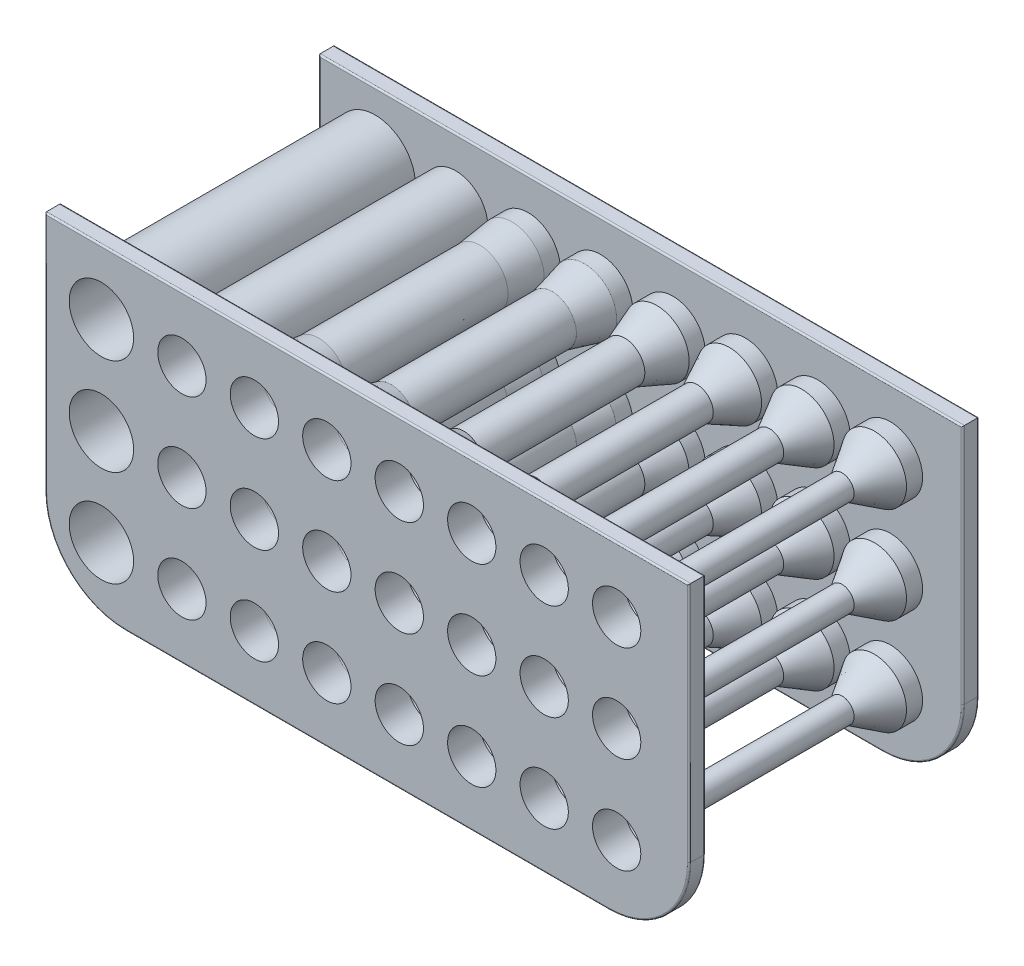
SolidWorks part; units mm, degrees
note: The reader was unsure of these and kept them because the rebuilt part matched: shared geometry of "Skizze1<3>", "Sketch7<3>".
ref_plane "Ebene vorne" through (0, 0, 0) normal (0, 0, 1) x (1, 0, 0)
ref_plane "Ebene oben" through (0, 0, 0) normal (0, 1, 0) x (1, 0, 0)
ref_plane "Ebene rechts" through (0, 0, 0) normal (1, 0, 0) x (0, 0, -1)
sketch "Skizze1" plane through (0, 0, 0) normal (0, 0, 1) x (1, 0, 0)
  line L0 (-40, 0) -> (40, 0) construction
  line L1 (-40, -16) -> (40, -16) construction
  line L2 (-40, -16) -> (-40, 16) construction
  line L3 (-40, 16) -> (40, 16) construction
  line L4 (40, -16) -> (40, 16) construction
  line L5 (-40, -16) -> (40, 16) construction
  line L6 (-40, 16) -> (40, -16) construction
  circle A12 centre (-33, 0) radius 4
  circle A14 centre (-23, 0) radius 3
  circle A22 centre (-14, 0) radius 2.5
  circle A26 centre (-5, 0) radius 2
  circle A32 centre (4, 0) radius 1.5
  circle A40 centre (13, 0) radius 1
  circle A48 centre (22, 0) radius 0.75
  circle A54 centre (31, 0) radius 0.5
  point P0 (0, 0)
  point P5 (0, 0)
  dimension "D5" = 7
  dimension "D6" = 17
  dimension "D7" = 8
  dimension "D8" = 26
  dimension "D9" = 6
  dimension "D10" = 35
  dimension "D11" = 44
  dimension "D12" = 53
  dimension "D13" = 62
  dimension "D14" = 71
  dimension "D17" = 5
  dimension "D21" = 4
  dimension "D27" = 3
  dimension "D35" = 2
  dimension "D43" = 1.5
  dimension "D49" = 1
  dimension "D1" = 32
  dimension "D2" = 80
extrude "Extrude-Thin2" add sketch "Skizze1" along normal mid plane 36 thin thin type one direction wall 1
ref_plane "Plane1" through (0, 0, 18) normal (0, 0, 1) x (1, 0, 0)
ref_plane "Plane2" through (0, 0, -18) normal (0, 0, 1) x (1, 0, 0)
sketch "Sketch1" plane through (0, 0, 18) normal (0, 0, 1) x (1, 0, 0)
  line L1 (-40, 20) -> (40, 20)
  line L2 (-40, 20) -> (-40, -20)
  line L3 (-40, -20) -> (40, -20)
  line L4 (40, 20) -> (40, -20)
  line L5 (-40, 20) -> (40, -20) construction
  line L6 (-40, -20) -> (40, 20) construction
  point P0 (0, 0)
  point P21 (0, 0)
  dimension "D1" = 80
  dimension "D2" = 40
extrude "Boss-Extrude1" add sketch "Sketch1" against normal blind 2
sketch "Sketch7" plane through (0, 0, 18) normal (0, 0, 1) x (1, 0, 0)
  circle A0 centre (31, 0) radius 4
  circle A1 centre (22, 0) radius 4
  circle A2 centre (13, 0) radius 4
  circle A3 centre (4, 0) radius 4
  circle A4 centre (-5, 0) radius 4
  circle A5 centre (-14, 0) radius 4
  circle A6 centre (-5, 0) radius 3 construction
  circle A7 centre (-14, 0) radius 3.5 construction
  point P16 (0, 0)
  point P17 (0, 0)
  dimension "D1" = 8
  dimension "D2" = 8
  dimension "D3" = 8
fillet "Fillet1" radius 10 2 edges at (40, -20, 17) (-40, -20, 17)
pattern_linear "LPattern2" count 2 spacing 34 along (0, 0, -1) of "Boss-Extrude1", "Fillet1"
extrude "Cut-Extrude1" cut sketch "Skizze1<3>" against normal mid plane 36
sketch "Skizze1<3>" plane through (0, 0, 0) normal (0, 0, 1) x (1, 0, 0) same geometry as "Skizze1"
extrude "Cut-Extrude2" cut sketch "Sketch7" against normal blind 8
extrude "Extrude-Thin3" add sketch "Sketch7<3>" against normal blind 4 thin thin type one direction reverse wall 1
sketch "Sketch7<3>" plane through (0, 0, 18) normal (0, 0, 1) x (1, 0, 0) same geometry as "Sketch7"
sketch "Sketch22" plane through (0, 0, 0) normal (0, 1, 0) x (1, 0, 0)
  line L0 (15, -10) -> (17, -14)
  line L1 (17, -14) -> (16, -14)
  line L2 (16, -14) -> (14, -10)
  line L3 (15, -10) -> (14, -10)
sketch "Sketch23" plane through (0, 0, 0) normal (0, 1, 0) x (1, 0, 0)
  line L0 (23.75, -10) -> (26, -14)
  line L1 (26, -14) -> (25, -14)
  line L2 (25, -14) -> (22.75, -10)
  line L3 (22.75, -10) -> (23.75, -10)
sketch "Sketch24" plane through (0, 0, 0) normal (0, 1, 0) x (1, 0, 0)
  line L0 (35, -14) -> (34, -14)
  line L1 (34, -14) -> (31.5, -10)
  line L2 (31.5, -10) -> (32.5, -10)
  line L3 (32.5, -10) -> (35, -14)
ref_axis "Axis2" through (4, 0, 14) along (0, 0, 1)
ref_axis "Axis3" through (22, 0, 14) along (0, 0, 1)
ref_axis "Axis4" through (13, 0, 14) along (0, 0, 1)
ref_axis "Axis5" through (31, 0, 14) along (0, 0, 1)
sketch "Sketch8" plane through (0, 0, 0) normal (0, 1, 0) x (1, 0, 0)
  line L0 (7, -14) -> (8, -14)
  line L1 (8, -14) -> (6.5, -10)
  line L2 (6.5, -10) -> (5.5, -10)
  line L3 (5.5, -10) -> (7, -14)
revolve "Revolve2" add sketch "Sketch8" angle 360 about axis through (4, 0, 14) along (0, 0, 1)
revolve "Revolve3" add sketch "Sketch22" angle 360 about axis through (13, 0, 14) along (0, 0, 1)
revolve "Revolve4" add sketch "Sketch23" angle 360 about axis through (22, 0, 14) along (0, 0, 1)
revolve "Revolve5" add sketch "Sketch24" angle 360 about axis through (31, 0, 14) along (0, 0, 1)
ref_axis "Achse1" through (-5, 0, 14) along (0, 0, 1)
ref_axis "Achse2" through (-14, 0, 14) along (0, 0, 1)
sketch "Skizze2" plane through (0, 0, 0) normal (0, 1, 0) x (1, 0, 0)
  line L0 (-2, -10) -> (-1, -14)
  line L1 (-1, -14) -> (-2, -14)
  line L2 (-2, -14) -> (-3, -10)
  line L3 (-3, -10) -> (-2, -10)
sketch "Skizze3" plane through (0, 0, 0) normal (0, 1, 0) x (1, 0, 0)
  line L0 (-10.5, -10) -> (-10, -14)
  line L1 (-10, -14) -> (-11, -14)
  line L2 (-11, -14) -> (-11.5, -10)
  line L3 (-11.5, -10) -> (-10.5, -10)
revolve "Rotation1" add sketch "Skizze2" angle 360 about axis through (-5, 0, 14) along (0, 0, 1)
revolve "Rotation2" add sketch "Skizze3" angle 360 about axis through (-14, 0, 14) along (0, 0, 1)
fillet "Fillet3" radius 0.2 56 edges at (-28, 0, -16) (-19, 0, -16) (-10.5, 0, -16) (-2, 0, -16) (6.5, 0, -16) (15, 0, -16) (23.75, 0, -16) (32.5, 0, -16) (-40, 5, -18) (0, 20, -18) (0, 20, -16) (-40, 5, -16) (-40, 5, 16) (0, 20, 16) (0, 20, 18) (-40, 5, 18) (0, -20, -16) (0, -20, -18) (40, 5, -16) (-37.0711, -17.0711, -16) (37.0711, -17.0711, -16) (40, 5, -18) (-37.0711, -17.0711, -18) (37.0711, -17.0711, -18) (-29, 0, -18) (-29, 0, 18) (-20, 0, -18) (-20, 0, 18) (-11.5, 0, -18) (-3, 0, -18) (5.5, 0, -18) (14, 0, -18) (22.75, 0, -18) (31.5, 0, -18) (-19, 0, 16) (35, 0, 16) (34, 0, 18) (26, 0, 16) (25, 0, 18) (17, 0, 16) (16, 0, 18) (8, 0, 16) (7, 0, 18) (-1, 0, 16) (-2, 0, 18) (-10, 0, 16) (-11, 0, 18) (0, -20, 18) (0, -20, 16) (40, 5, 18) (-37.0711, -17.0711, 18) (37.0711, -17.0711, 18) (40, 5, 16) (-37.0711, -17.0711, 16) (37.0711, -17.0711, 16) (-28, 0, 16)
mirror "Spiegeln1" about plane through (0, 0, 0) normal (0, 0, 1) of "Extrude-Thin3", "Cut-Extrude2", "Revolve2", "Revolve3", "Revolve4", "Revolve5", "Rotation1", "Rotation2"
pattern_linear "Lineares Muster1" count 2 spacing 12 along (0, -1, 0) count 2 spacing 12 along (0, 1, 0) of "Rotation2", "Rotation1", "Revolve5", "Revolve4", "Revolve3", "Revolve2", "Extrude-Thin3", "Cut-Extrude2", "Cut-Extrude1", "Extrude-Thin2", "Spiegeln1"
